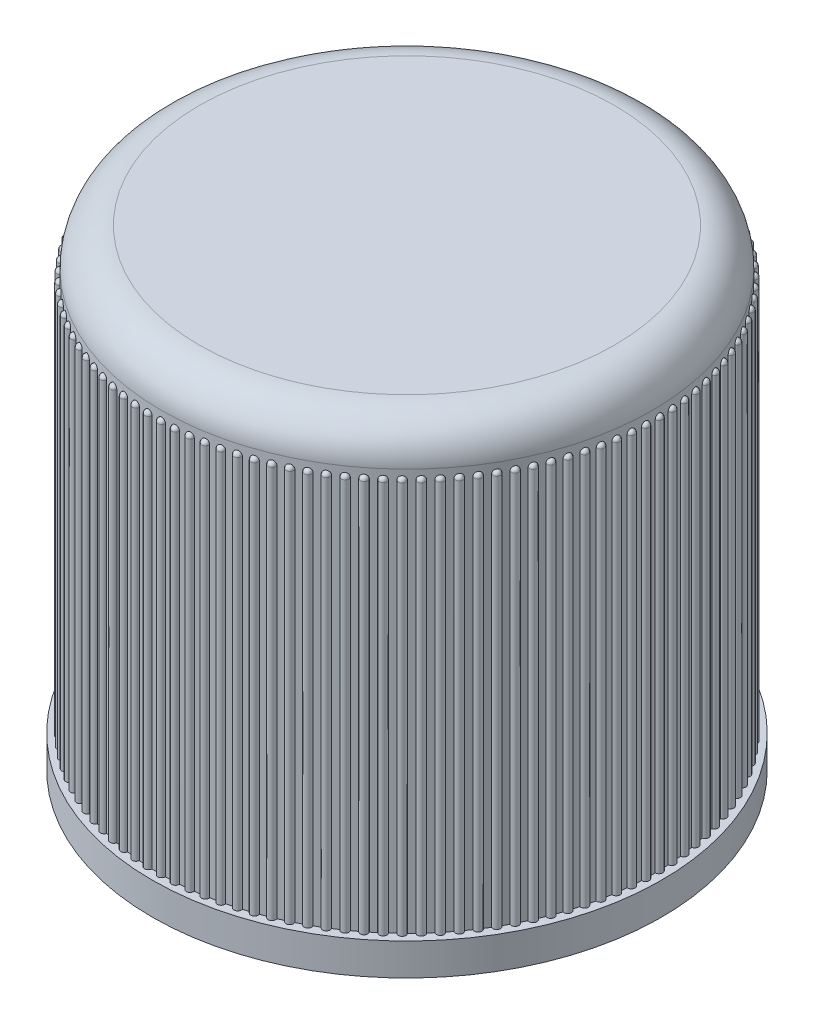
SolidWorks part; units mm, degrees
ref_plane "Front Plane" through (0, 0, 0) normal (0, 0, 1) x (1, 0, 0)
ref_plane "Top Plane" through (0, 0, 0) normal (0, 1, 0) x (1, 0, 0)
ref_plane "Right Plane" through (0, 0, 0) normal (1, 0, 0) x (0, 0, -1)
sketch "Sketch1" plane through (0, 0, 0) normal (0, 1, 0) x (1, 0, 0)
  circle A0 centre (0, 0) radius 13.5
  dimension "D1" = 27
extrude "Boss-Extrude1" add sketch "Sketch1" along normal blind 25
sketch "Sketch2" plane through (0, 25, 0) normal (0, 1, 0) x (1, 0, 0)
  circle A1 centre (0, 0) radius 13
  circle A2 centre (0, 0) radius 13.5
  circle A3 centre (0, 0) radius 13.5
  dimension "D1" = 0
  dimension "D2" = 0.5
extrude "Cut-Extrude1" cut sketch "Sketch2" against normal blind 23.3
fillet "Fillet1" radius 2 1 edges at (0, 25, 13)
shell "Shell1" thickness 0.5
sketch "Sketch6" plane through (0, 1.2, 0) normal (0, -1, 0) x (1, 0, 0)
  circle A2 centre (0, 0) radius 12.5
  circle A3 centre (0, 0) radius 12.5
  circle A5 centre (0, 0) radius 13.5
  circle A6 centre (0, 0) radius 13.5
  dimension "D1" = 0
  dimension "D2" = 0
extrude "Boss-Extrude3" add sketch "Sketch6" along normal up to surface (1.2 mm away) up to face at (0, 0, 13)
sketch "Sketch3" plane through (0, 1.7, 0) normal (0, 1, 0) x (1, 0, 0)
  circle A0 centre (0, -13) radius 0.2
  circle A1 centre (0, 0) radius 13 construction
  dimension "D1" = 0.4
extrude "Boss-Extrude2" add sketch "Sketch3" along normal blind 21
fillet "Fillet2" radius 0.2 1 edges at (0, 22.7, 13.2)
pattern_circular "CirPattern1" count 114 over 360 about axis through (0, 0, 0) along (0, 1, 0) of "Fillet2", "Boss-Extrude2"
